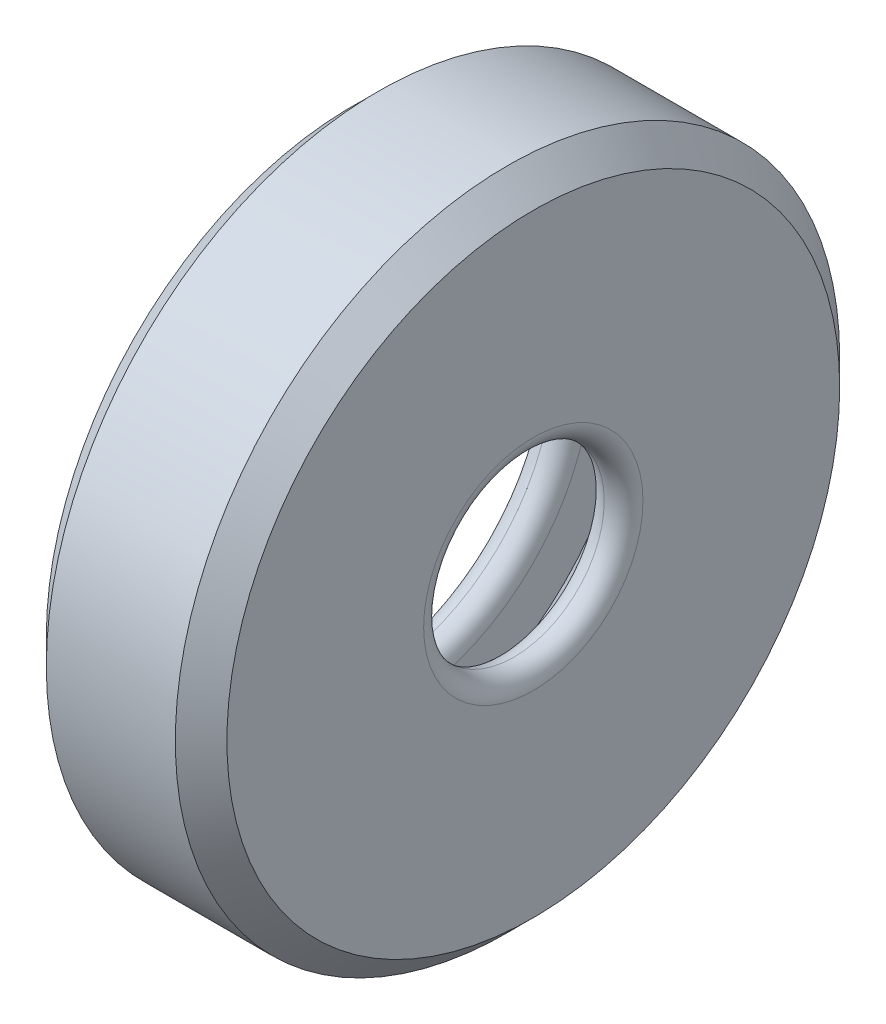
SolidWorks part; units mm, degrees
material "3D_printed_PLA"
ref_plane "Front Plane" through (0, 0, 0) normal (0, 0, 1) x (1, 0, 0)
ref_plane "Top Plane" through (0, 0, 0) normal (0, 1, 0) x (1, 0, 0)
ref_plane "Right Plane" through (0, 0, 0) normal (1, 0, 0) x (0, 0, -1)
sketch "Sketch1" plane through (0, 0, 0) normal (0, 0, 1) x (1, 0, 0)
  line L0 (0, 0) -> (-32.1309, 0) construction
  line L1 (-7, 14) -> (-7, 25.75)
  line L2 (-7, 25.75) -> (7, 25.75)
  line L3 (7, 25.75) -> (7, 14)
  line L4 (7, 14) -> (4, 14) construction
  line L5 (4, 14) -> (4, 21)
  line L6 (4, 21) -> (-4, 21)
  line L7 (-4, 21) -> (-4, 14)
  line L8 (-4, 14) -> (-7, 14)
  line L9 (-4, 14) -> (0, 0) construction
  line L10 (0, 0) -> (4, 14) construction
  line L11 (4, 14) -> (4, 7)
  line L12 (4, 7) -> (7, 7)
  line L13 (7, 7) -> (7, 14)
  dimension "D1" = 51.5
  dimension "D2" = 14
  dimension "D3" = 3
  dimension "D4" = 42
  dimension "D5" = 28
  dimension "D6" = 14
revolve "Revolve1" add sketch "Sketch1" angle 360 about L0
chamfer "Chamfer1" distance 2 angle 45 4 edges at (-7, 0, -25.75) (7, 0, -25.75) (-4, 0, -21) (4, 0, -21)
fillet "Fillet1" radius 1.5 4 edges at (-7, 0, -14) (-4, 0, -14) (4, 0, -7) (7, 0, -7)
